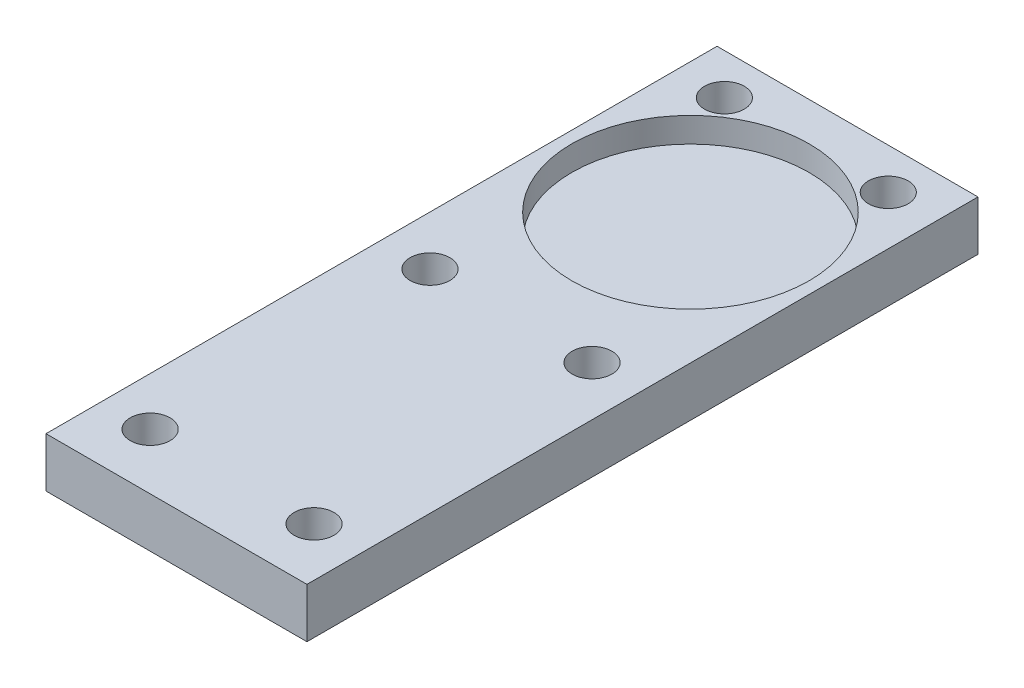
SolidWorks part; units mm, degrees
ref_plane "Front Plane" through (0, 0, 0) normal (0, 0, 1) x (1, 0, 0)
ref_plane "Top Plane" through (0, 0, 0) normal (0, 1, 0) x (1, 0, 0)
ref_plane "Right Plane" through (0, 0, 0) normal (1, 0, 0) x (0, 0, -1)
sketch "Sketch2" plane through (0, 0, 0) normal (0, 0, 1) x (1, 0, 0)
  line L0 (8.9091, -10.9) -> (8.9091, 3)
  line L1 (8.9091, 3) -> (13.9091, -10.9)
  line L2 (13.9091, -10.9) -> (8.9091, -10.9)
  line L3 (-1.5909, -8.1) -> (-1.5909, -13.7) construction
  line L4 (-17.0909, -10.9) -> (-12.0909, -10.9)
  line L5 (-12.0909, 3) -> (-17.0909, -10.9)
  line L6 (-12.0909, -10.9) -> (-12.0909, 3)
  line L7 (-26.5909, -10.9) -> (23.4091, -10.9)
  line L8 (23.4091, -10.9) -> (23.4091, -14.9)
  line L9 (23.4091, -14.9) -> (-26.5909, -14.9)
  line L10 (-26.5909, -14.9) -> (-26.5909, -10.9)
  point P16 (-1.5909, -10.9)
  dimension "D1" = 5
  dimension "D2" = 50
  dimension "D3" = 4
  dimension "D4" = 10.5
  dimension "D5" = 1.5909
  dimension "D6" = 10.9
  dimension "D7" = 70.216
extrude "Boss-Extrude1" add sketch "Sketch2" against normal blind 54 contours L4 L6 L5 | L10 L9 L8 L7 L2 L4 | L2 L0 L1 region at (-1.5909, -12.9, 0) region at (-13.7576, -6.2667, 0)
sketch "Sketch3" plane through (0, -10.9, 0) normal (0, 1, 0) x (1, 0, 0)
  line L0 (-12.0909, 54) -> (-12.0909, 0) construction
  line L1 (-12.0909, 54) -> (8.9091, 54) construction
  circle A0 centre (-1.5909, 41.36) radius 9.55
  dimension "D1" = 19.1
  dimension "D2" = 10.5
  dimension "D3" = 12.64
extrude "Cut-Extrude1" cut sketch "Sketch3" against normal blind 2
sketch "Sketch6" plane through (0, -14.9, 0) normal (0, -1, 0) x (1, 0, 0)
  circle A0 centre (5.8804, -26.92) radius 1.6
  circle A1 centre (-7.1596, -26.92) radius 1.6
  dimension "D1" = 3.2
hole_wizard "CSK for M3 Flat Head Machine Screw1" positions "Sketch7" profile "Sketch8" countersink size "M3" standard "ANSI Metric"
sketch "Sketch7" plane through (0, -14.9, 0) normal (0, -1, 0) x (-1, 0, 0)
  line L0 (1.5909, 41.36) -> (1.5909, 10.913) construction
  line L1 (12.0909, 54) -> (-8.9091, 54) construction
  point P0 (8.1109, 26.92)
  point P3 (-4.9291, 26.92)
  dimension "D1" = 6.52
  dimension "D2" = 6.52
  dimension "D3" = 27.08
sketch "Sketch8" plane through (-8.1109, -14.9, -26.92) normal (1, 0, 0) x (0, 0, -1)
  line L0 (0, 0) -> (0, 5.9614)
  line L1 (0, 5.9614) -> (1.6, 5)
  line L2 (1.6, 5) -> (1.6, 1.55)
  line L3 (1.6, 1.55) -> (3.15, 0)
  line L5 (3.15, 0) -> (0, 0)
  line L6 (-1.6, 1.55) -> (-3.15, 0) construction
  line L10 (0, 5.9614) -> (-1.6, 5) construction
  line L11 (0, -6.35) -> (0, 107.95) construction
  dimension "Hole Dia." = 3.2
  dimension "Hole Depth" = 5
  dimension "Near C'Sink Dia." = 6.3
  dimension "Near C'Sink Angle" = 90
  dimension "Drill Angle" = 118
sketch "Sketch17" plane through (0, 0, 0) normal (0, 0, 1) x (1, 0, 0)
  line L0 (23.4091, -14.9) -> (-26.5909, -14.9) construction
  line L1 (-12.0909, -14.9) -> (-26.5909, -14.9)
  line L2 (-12.0909, -14.9) -> (-12.0909, 3)
  line L3 (-12.0909, 3) -> (-26.5909, 3)
  line L4 (-26.5909, -14.9) -> (-26.5909, 3)
  line L5 (23.4091, -10.9) -> (23.4091, -14.9) construction
  line L6 (8.9091, -14.9) -> (23.4091, -14.9)
  line L7 (8.9091, -14.9) -> (8.9091, 3)
  line L8 (8.9091, 3) -> (23.4091, 3)
  line L9 (23.4091, -14.9) -> (23.4091, 3)
  line L10 (8.9091, -10.9) -> (8.9091, 3) construction
  line L12 (-26.5909, -14.9) -> (-26.5909, -10.9) construction
extrude "Cut-Extrude3" cut sketch "Sketch17" against normal through all
sketch "Sketch18" plane through (0, -14.9, 0) normal (0, 1, 0) x (1, 0, 0)
  circle A0 centre (-8.2109, 50.71) radius 1.6
  circle A1 centre (4.9786, 50.71) radius 1.6
  circle A2 centre (4.9786, 4.5) radius 1.6
  circle A3 centre (-8.2109, 4.5) radius 1.6
  dimension "D1" = 3.2
hole_wizard "CSK for M3 Flat Head Machine Screw3" positions "Sketch19" profile "Sketch20" countersink size "M3" standard "ANSI Metric"
sketch "Sketch19" plane through (0, -14.9, 0) normal (0, -1, 0) x (-1, 0, 0)
  point P0 (-4.9786, 50.71)
  point P3 (8.2109, 50.71)
  point P6 (8.2109, 4.5)
  point P9 (-4.9786, 4.5)
sketch "Sketch20" plane through (4.9786, -14.9, -50.71) normal (1, 0, 0) x (0, 0, -1)
  line L0 (0, 0) -> (0, 5.9614)
  line L1 (0, 5.9614) -> (1.6, 5)
  line L2 (1.6, 5) -> (1.6, 1.55)
  line L3 (1.6, 1.55) -> (3.15, 0)
  line L5 (3.15, 0) -> (0, 0)
  line L6 (-1.6, 1.55) -> (-3.15, 0) construction
  line L10 (0, 5.9614) -> (-1.6, 5) construction
  line L11 (0, -6.35) -> (0, 107.95) construction
  dimension "Hole Dia." = 3.2
  dimension "Hole Depth" = 5
  dimension "Near C'Sink Dia." = 6.3
  dimension "Near C'Sink Angle" = 90
  dimension "Drill Angle" = 118
sketch "Sketch10" plane through (23.4091, 0, 0) normal (1, 0, 0) x (0, 0, -1)
  line L0 (54, -10.9) -> (54, 3) construction
  line L1 (54, 3) -> (0, 3) construction
  line L2 (26.92, -14.9) -> (26.92, -5.4) construction
  line L3 (25.32, -14.9) -> (28.52, -14.9) construction
  circle A0 centre (48.5, -5.4) radius 1.5
  circle A1 centre (5.34, -5.4) radius 1.5
  dimension "D1" = 3
  dimension "D2" = 5.5
  dimension "D3" = 8.4
sketch "Sketch13" plane through (0, 0, 0) normal (0, 0, 1) x (1, 0, 0)
  line L0 (10.9091, -2.25) -> (10.9091, -8.55)
  line L2 (8.9091, -10.9) -> (8.9091, 3) construction
  point P2 (10.9091, -5.4)
  dimension "D1" = 6.3
  dimension "D2" = 2
ref_plane "Plane1" through (10.9091, 0, 0) normal (1, 0, 0) x (0, 0, -1)
hole_wizard "CSK for M3 Flat Head Machine Screw2" positions "Sketch14" profile "Sketch15" countersink size "M3" standard "ANSI Metric" rebuild error yes
sketch "Sketch14" plane through (10.9091, 0, 0) normal (1, 0, 0) x (0, 0, -1)
  line L0 (54, -10.9) -> (0, -10.9) construction
  line L1 (0, 3) -> (0, -10.9) construction
  line L2 (27, 3) -> (27, -14.9) construction
  line L3 (54, 3) -> (0, 3) construction
  line L4 (54, -14.9) -> (0, -14.9) construction
  line L6 (54, 3) -> (54, -10.9) construction
  point P0 (5.34, -6.5)
  point P3 (48.5, -6.5)
  dimension "D1" = 4.4
  dimension "D2" = 5.34
  dimension "D3" = 5.5
sketch "Sketch15" plane through (10.9091, -6.5, -5.34) normal (0, 1, 0) x (0, 0, -1)
  line L0 (0, 0) -> (0, 5.9614)
  line L1 (0, 5.9614) -> (1.6, 5)
  line L2 (1.6, 5) -> (1.6, 1.55)
  line L3 (1.6, 1.55) -> (3.15, 0)
  line L5 (3.15, 0) -> (0, 0)
  line L6 (-1.6, 1.55) -> (-3.15, 0) construction
  line L10 (0, 5.9614) -> (-1.6, 5) construction
  line L11 (0, -6.35) -> (0, 107.95) construction
  dimension "Hole Dia." = 3.2
  dimension "Hole Depth" = 5
  dimension "Near C'Sink Dia." = 6.3
  dimension "Near C'Sink Angle" = 90
  dimension "Drill Angle" = 118
sketch "Sketch16" plane through (10.9091, 0, 0) normal (-1, 0, 0) x (0, 0, 1)
  circle A1 centre (-5.34, -6.5) radius 3.15
  circle A2 centre (-5.34, -6.5) radius 3.15
  circle A3 centre (-48.5, -6.5) radius 3.15
  circle A5 centre (-48.5, -6.5) radius 3.15
  dimension "D1" = 0
  dimension "D2" = 0
extrude "Cut-Extrude2" cut sketch "Sketch16" against normal blind 10 rebuild error yes
ref_plane "Plane2" through (-1.5909, 0, 0) normal (-1, 0, 0) x (0, 0, 1)
mirror "Mirror1" about plane through (-1.5909, 0, 0) normal (-1, 0, 0) rebuild error yes
fillet "Fillet1" radius 0.2 rebuild error yes
